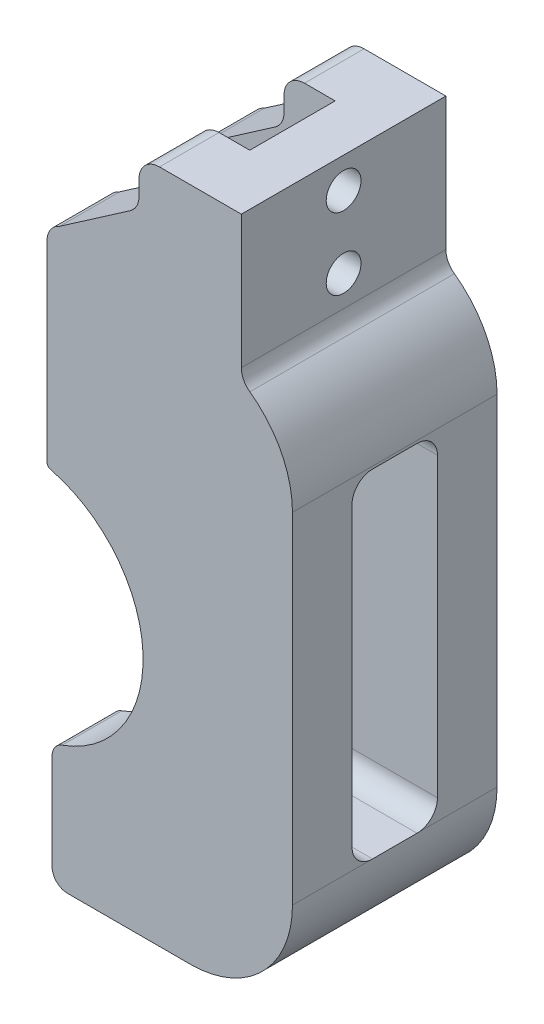
SolidWorks part; units mm, degrees
material "ABS"
ref_plane "前视基准面" through (0, 0, 0) normal (0, 0, 1) x (1, 0, 0)
ref_plane "上视基准面" through (0, 0, 0) normal (0, 1, 0) x (1, 0, 0)
ref_plane "右视基准面" through (0, 0, 0) normal (1, 0, 0) x (0, 0, -1)
sketch "草图1" plane through (0, 0, 0) normal (0, 0, 1) x (1, 0, 0)
  line L0 (0, 0) -> (10, 0)
  line L3 (0, 0) -> (0, -4.5431)
  line L6 (-9, -9.9117) -> (-9, -30.8656)
  line L7 (10, 0) -> (10, -15)
  line L8 (10, -15) -> (29.096, -15)
  line L9 (29.096, -15) -> (29.096, -66)
  line L10 (0, -4.5431) -> (-7.763, -9.9117)
  line L11 (-7.763, -9.9117) -> (-9, -9.9117)
  line L12 (19.5, -30.6) -> (19.5, -56) construction
  line L13 (-11.5, -54.4) -> (-11.5, -66)
  line L14 (-11.5, -66) -> (29.096, -66)
  circle A0 centre (-11.5, -42.5) radius 11.9 construction
  arc A1 (-9, -30.8656) -> (-11.5, -54.4) centre (-11.5, -42.5) cw
  circle A2 centre (19.5, -30.6) radius 1.7
  circle A3 centre (19.5, -56) radius 1.7
  dimension "D2" = 23.8
  dimension "D6" = 3.4
  dimension "D7" = 3.4
  dimension "D10" = 42.5
  dimension "D12" = 15.6
  dimension "D13" = 10
  dimension "D1" = 11.5
  dimension "D3" = 11.5
  dimension "D4" = 10
  dimension "D5" = 31
  dimension "D8" = 9
  dimension "D9" = 25.4
  dimension "D11" = 15
extrude "凸台-拉伸1" add sketch "草图1" along normal blind 20
sketch "草图2" plane through (0, 0, 0) normal (0, 1, 0) x (1, 0, 0)
  line L1 (-26.6435, -5.825) -> (5, -5.825)
  line L2 (-26.6435, -5.825) -> (-26.6435, -14.175)
  line L3 (-26.6435, -14.175) -> (5, -14.175)
  line L4 (5, -5.825) -> (5, -14.175)
  line L7 (5, -10) -> (10, -10) construction
  line L8 (10, -20) -> (10, 0) construction
  line L9 (0, -20) -> (0, 0) construction
  dimension "D1" = 5
  dimension "D2" = 8.35
extrude "切除-拉伸1" cut sketch "草图2" against normal through all
sketch "草图4" plane through (10, 0, 0) normal (1, 0, 0) x (0, 0, -1)
  line L0 (-10, 0) -> (-10, -3) construction
  line L1 (-20, 0) -> (0, 0) construction
  line L2 (-10, -3) -> (-10, -10) construction
  circle A0 centre (-10, -3) radius 1.7
  circle A1 centre (-10, -10) radius 1.7
  dimension "D2" = 3.4
  dimension "D3" = 3.4
  dimension "D1" = 7
  dimension "D4" = 3
extrude "切除-拉伸3" cut sketch "草图4" against normal through all
fillet "圆角1" radius 0.5 4 edges at (-9, -30.8656, 17.0875) (-9, -30.8656, 2.9125) (-11.5, -66, 2.9125) (-11.5, -66, 17.0875)
fillet "圆角2" radius 2 9 edges at (-9, -9.9117, 2.9125) (-9, -9.9117, 17.0875) (0, -4.5431, 17.0875) (0, -4.5431, 2.9125) (0, 0, 2.9125) (0, 0, 17.0875) (10, -15, 10) (29.096, -15, 10) (29.096, -66, 10)
sketch "草图5" plane through (0, 0, 20) normal (0, 0, 1) x (1, 0, 0)
  line L0 (-11.5, -54.4) -> (-11.5, -65.5) construction
  line L1 (-12.0715, -48.1848) -> (-8.5, -48.1848)
  line L2 (-12.0715, -48.1848) -> (-12.0715, -67.4708)
  line L3 (-12.0715, -67.4708) -> (-8.5, -67.4708)
  line L4 (-8.5, -48.1848) -> (-8.5, -67.4708)
  dimension "D1" = 3
extrude "切除-拉伸4" cut sketch "草图5" against normal through all
fillet "圆角3" radius 1.5 4 edges at (-8.5, -54.0156, 2.9125) (-8.5, -54.0156, 17.0875) (-8.5, -66, 2.9125) (-8.5, -66, 17.0875)
sketch "草图6" plane through (0, 0, 0) normal (0, 0, -1) x (-1, 0, 0)
  line L0 (-10, -13) -> (-10, 0) construction
  line L1 (-29.5836, -11.1604) -> (-15, -11.1604)
  line L2 (-29.5836, -11.1604) -> (-29.5836, -68.8399)
  line L3 (-29.5836, -68.8399) -> (-15, -68.8399)
  line L4 (-15, -11.1604) -> (-15, -68.8399)
  dimension "D1" = 5
extrude "切除-拉伸5" cut sketch "草图6" against normal through all
fillet "圆角4" radius 10 2 edges at (15, -66, 10) (15, -15, 10)
sketch "草图7" plane through (5, 0, 0) normal (-1, 0, 0) x (0, 0, 1)
  line L0 (5.825, -66) -> (5.825, 0) construction
  line L1 (5.825, -23) -> (14.175, -23)
  line L2 (5.825, -23) -> (5.825, -56)
  line L3 (5.825, -56) -> (14.175, -56)
  line L4 (14.175, -23) -> (14.175, -56)
  line L5 (14.175, -66) -> (14.175, 0) construction
  line L6 (14.175, -66) -> (5.825, -66) construction
  point P10 (10, -66)
  dimension "D1" = 10
  dimension "D2" = 33
extrude "切除-拉伸6" cut sketch "草图7" against normal through all
fillet "圆角5" radius 2 4 edges at (10, -56, 14.175) (10, -23, 14.175) (10, -23, 5.825) (10, -56, 5.825)
